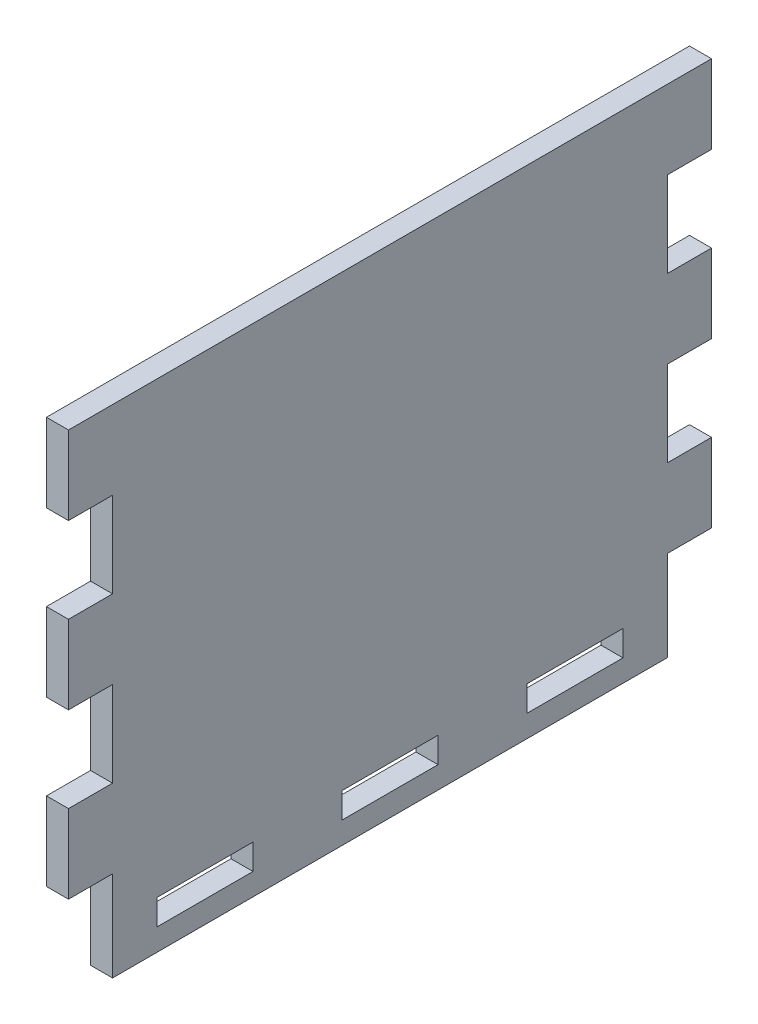
SolidWorks part; units mm, degrees
material "ABS"
ref_plane "Front Plane" through (0, 0, 0) normal (0, 0, 1) x (1, 0, 0)
ref_plane "Top Plane" through (0, 0, 0) normal (0, 1, 0) x (1, 0, 0)
ref_plane "Right Plane" through (0, 0, 0) normal (1, 0, 0) x (0, 0, -1)
sketch "Sketch2" plane through (-43.425, 0, 0) normal (-1, 0, 0) x (0, 0, 1)
  line L0 (92.7098, 28.4544) -> (92.7098, 40.2725) construction
  line L1 (92.7098, 40.2725) -> (86.3598, 40.2725) construction
  line L2 (86.3598, 40.2725) -> (86.3598, 28.4544) construction
  line L3 (86.3598, 28.4544) -> (92.7098, 28.4544) construction
  line L4 (92.7098, 4.818) -> (92.7098, 16.6362) construction
  line L5 (92.7098, 16.6362) -> (86.3598, 16.6362) construction
  line L6 (86.3598, 16.6362) -> (86.3598, 4.818) construction
  line L7 (86.3598, 4.818) -> (92.7098, 4.818) construction
  line L8 (92.7098, -18.8184) -> (92.7098, -7.0002) construction
  line L9 (92.7098, -7.0002) -> (86.3598, -7.0002) construction
  line L10 (86.3598, -7.0002) -> (86.3598, -18.8184) construction
  line L11 (86.3598, -18.8184) -> (92.7098, -18.8184) construction
  line L12 (79.6923, -24.9775) -> (66.3573, -24.9775) construction
  line L13 (6.35, 40.0225) -> (0, 40.0225)
  line L14 (66.3573, -28.1525) -> (79.6923, -28.1525) construction
  line L15 (0, 40.0225) -> (0, 28.7044)
  line L16 (53.0224, -28.1525) -> (66.3573, -28.1525) construction
  line L17 (66.3573, -28.1525) -> (66.3573, -24.9775) construction
  line L18 (66.3573, -24.9775) -> (53.0224, -24.9775) construction
  line L19 (0, 28.7044) -> (6.35, 28.7044)
  line L20 (53.0224, -24.9775) -> (39.6874, -24.9775) construction
  line L21 (6.35, 28.7044) -> (6.35, 16.3862)
  line L22 (39.6874, -28.1525) -> (53.0224, -28.1525) construction
  line L23 (53.0224, -28.1525) -> (53.0224, -24.9775) construction
  line L24 (26.3524, -28.1525) -> (39.6874, -28.1525) construction
  line L25 (39.6874, -28.1525) -> (39.6874, -24.9775) construction
  line L26 (39.6874, -24.9775) -> (26.3524, -24.9775) construction
  line L27 (6.35, 16.3862) -> (0, 16.3862)
  line L28 (26.3524, -24.9775) -> (13.0175, -24.9775) construction
  line L29 (0, 16.3862) -> (0, 5.068)
  line L30 (13.0175, -28.1525) -> (26.3524, -28.1525) construction
  line L31 (26.3524, -28.1525) -> (26.3524, -24.9775) construction
  line L32 (6.35, -28.1525) -> (13.0175, -28.1525) construction
  line L33 (13.0175, -28.1525) -> (13.0175, -24.9775) construction
  line L34 (13.0175, -24.9775) -> (6.35, -24.9775) construction
  line L35 (6.35, -24.9775) -> (6.35, -28.1525) construction
  line L36 (0, -7.0002) -> (0, -18.8184) construction
  line L37 (0, -18.8184) -> (6.35, -18.8184) construction
  line L38 (6.35, -18.8184) -> (6.35, -7.0002) construction
  line L39 (6.35, -7.0002) -> (0, -7.0002) construction
  line L40 (0, 16.6362) -> (0, 4.818) construction
  line L41 (0, 4.818) -> (6.35, 4.818) construction
  line L42 (6.35, 4.818) -> (6.35, 16.6362) construction
  line L43 (6.35, 16.6362) -> (0, 16.6362) construction
  line L44 (0, 40.2725) -> (0, 28.4544) construction
  line L45 (0, 28.4544) -> (6.35, 28.4544) construction
  line L46 (6.35, 28.4544) -> (6.35, 40.2725) construction
  line L47 (6.35, 40.2725) -> (0, 40.2725) construction
  line L48 (92.7098, 28.4544) -> (92.7098, 40.2725) construction
  line L49 (92.7098, 40.2725) -> (86.3598, 40.2725) construction
  line L50 (86.3598, 40.2725) -> (86.3598, 28.4544) construction
  line L51 (86.3598, 28.4544) -> (92.7098, 28.4544) construction
  line L52 (92.7098, 4.818) -> (92.7098, 16.6362) construction
  line L53 (92.7098, 16.6362) -> (86.3598, 16.6362) construction
  line L54 (86.3598, 16.6362) -> (86.3598, 4.818) construction
  line L55 (86.3598, 4.818) -> (92.7098, 4.818) construction
  line L56 (92.7098, -18.8184) -> (92.7098, -7.0002) construction
  line L57 (92.7098, -7.0002) -> (86.3598, -7.0002) construction
  line L58 (86.3598, -7.0002) -> (86.3598, -18.8184) construction
  line L59 (86.3598, -18.8184) -> (92.7098, -18.8184) construction
  line L60 (79.6923, -24.9775) -> (66.3573, -24.9775) construction
  line L62 (66.3573, -28.1525) -> (79.6923, -28.1525) construction
  line L64 (53.0224, -28.1525) -> (66.3573, -28.1525) construction
  line L65 (66.3573, -28.1525) -> (66.3573, -24.9775) construction
  line L66 (66.3573, -24.9775) -> (53.0224, -24.9775) construction
  line L68 (53.0224, -24.9775) -> (39.6874, -24.9775) construction
  line L70 (39.6874, -28.1525) -> (53.0224, -28.1525) construction
  line L71 (53.0224, -28.1525) -> (53.0224, -24.9775) construction
  line L72 (26.3524, -28.1525) -> (39.6874, -28.1525) construction
  line L73 (39.6874, -28.1525) -> (39.6874, -24.9775) construction
  line L74 (39.6874, -24.9775) -> (26.3524, -24.9775) construction
  line L76 (26.3524, -24.9775) -> (13.0175, -24.9775) construction
  line L78 (13.0175, -28.1525) -> (26.3524, -28.1525) construction
  line L79 (26.3524, -28.1525) -> (26.3524, -24.9775) construction
  line L80 (6.35, -28.1525) -> (13.0175, -28.1525) construction
  line L81 (13.0175, -28.1525) -> (13.0175, -24.9775) construction
  line L82 (13.0175, -24.9775) -> (6.35, -24.9775) construction
  line L83 (6.35, -24.9775) -> (6.35, -28.1525) construction
  line L84 (0, -7.0002) -> (0, -18.8184) construction
  line L85 (0, -18.8184) -> (6.35, -18.8184) construction
  line L86 (6.35, -18.8184) -> (6.35, -7.0002) construction
  line L87 (6.35, -7.0002) -> (0, -7.0002) construction
  line L88 (0, 16.6362) -> (0, 4.818) construction
  line L89 (0, 4.818) -> (6.35, 4.818) construction
  line L90 (6.35, 4.818) -> (6.35, 16.6362) construction
  line L91 (6.35, 16.6362) -> (0, 16.6362) construction
  line L92 (0, 40.2725) -> (0, 28.4544) construction
  line L93 (0, 28.4544) -> (6.35, 28.4544) construction
  line L94 (6.35, 28.4544) -> (6.35, 40.2725) construction
  line L95 (6.35, 40.2725) -> (0, 40.2725) construction
  line L96 (0, 5.068) -> (6.35, 5.068)
  line L97 (6.35, 5.068) -> (6.35, -7.2502)
  line L98 (6.35, -7.2502) -> (0, -7.2502)
  line L99 (0, -7.2502) -> (0, -18.5684)
  line L100 (79.6923, -28.1525) -> (86.3598, -28.1525)
  line L101 (86.3598, -28.1525) -> (86.3598, -24.9775)
  line L102 (86.3598, -24.9775) -> (79.6923, -24.9775)
  line L103 (79.6923, -24.9775) -> (79.6923, -28.1525)
  line L104 (79.6923, -28.1525) -> (86.3598, -28.1525) construction
  line L105 (86.3598, -28.1525) -> (86.3598, -24.9775) construction
  line L106 (86.3598, -24.9775) -> (79.6923, -24.9775) construction
  line L107 (79.6923, -24.9775) -> (79.6923, -28.1525) construction
  line L108 (0, -18.5684) -> (6.35, -18.5684)
  line L109 (6.35, -18.5684) -> (6.35, -31.5775)
  line L110 (6.35, -31.5775) -> (86.3598, -31.5775)
  line L111 (86.3598, -31.5775) -> (86.3598, -18.5684)
  line L112 (86.3598, -18.5684) -> (92.7098, -18.5684)
  line L113 (92.7098, -18.5684) -> (92.7098, -7.2502)
  line L114 (92.7098, -7.2502) -> (86.3598, -7.2502)
  line L115 (86.3598, -7.2502) -> (86.3598, 5.068)
  line L116 (86.3598, 5.068) -> (92.7098, 5.068)
  line L117 (92.7098, 5.068) -> (92.7098, 16.3862)
  line L118 (92.7098, 16.3862) -> (86.3598, 16.3862)
  line L119 (86.3598, 16.3862) -> (86.3598, 28.7044)
  line L120 (86.3598, 28.7044) -> (92.7098, 28.7044)
  line L121 (92.7098, 28.7044) -> (92.7098, 40.0225)
  line L122 (92.7098, 40.0225) -> (86.3598, 40.0225)
  line L123 (86.3598, 40.0225) -> (6.35, 40.0225)
  line L124 (3.175, 40.2725) -> (3.175, 40.0225) construction
  line L125 (12.7675, -24.7275) -> (26.6024, -24.7275)
  line L126 (12.7675, -24.7275) -> (12.7675, -28.4025)
  line L127 (12.7675, -28.4025) -> (26.6024, -28.4025)
  line L128 (26.6024, -24.7275) -> (26.6024, -28.4025)
  line L129 (39.4374, -24.7275) -> (53.2724, -24.7275)
  line L130 (39.4374, -24.7275) -> (39.4374, -28.4025)
  line L131 (39.4374, -28.4025) -> (53.2724, -28.4025)
  line L132 (53.2724, -24.7275) -> (53.2724, -28.4025)
  line L133 (66.1073, -24.7275) -> (79.9423, -24.7275)
  line L134 (66.1073, -24.7275) -> (66.1073, -28.4025)
  line L135 (66.1073, -28.4025) -> (79.9423, -28.4025)
  line L136 (79.9423, -24.7275) -> (79.9423, -28.4025)
  line L137 (6.35, -31.5775) -> (0, -31.5775) construction
  line L138 (3.175, 28.7044) -> (3.175, 28.4544) construction
  line L139 (19.685, -24.7275) -> (19.685, -24.9775) construction
  line L140 (3.175, 16.6362) -> (3.175, 16.3862) construction
  line L141 (26.3524, -26.565) -> (26.6024, -26.565) construction
  line L142 (3.175, 5.068) -> (3.175, 4.818) construction
  line L143 (19.685, -28.1525) -> (19.685, -28.4025) construction
  line L144 (3.175, -7.0002) -> (3.175, -7.2502) construction
  line L145 (13.0175, -26.565) -> (12.7675, -26.565) construction
  line L146 (3.175, -18.5684) -> (3.175, -18.8184) construction
  line L147 (39.6874, -26.565) -> (39.4374, -26.565) construction
  line L148 (66.3573, -26.565) -> (66.1073, -26.565) construction
  dimension "D2" = 0.25
  dimension "D1" = 0
extrude "Boss-Extrude1" add sketch "Sketch2" against normal offset from surface (3.175 mm away) 0.25
